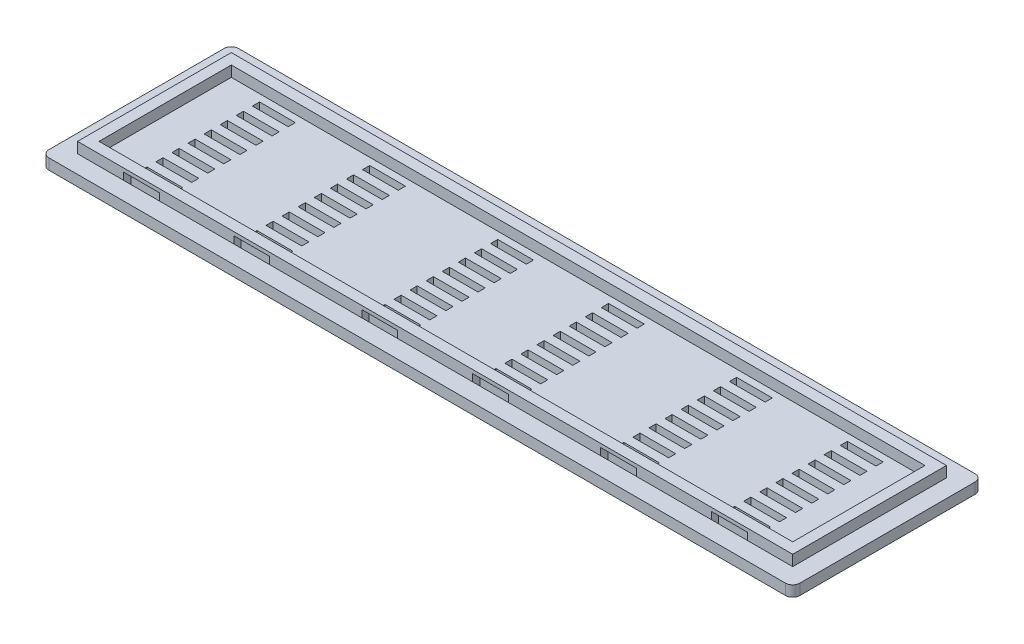
SolidWorks part; units mm, degrees
material "PET"
ref_plane "Спереди" through (0, 0, 0) normal (0, 0, 1) x (1, 0, 0)
ref_plane "Сверху" through (0, 0, 0) normal (0, 1, 0) x (1, 0, 0)
ref_plane "Справа" through (0, 0, 0) normal (1, 0, 0) x (0, 0, -1)
other "Configuration Table"
sketch "Основание & крышка" plane through (0, 0, 0) normal (0, 1, 0) x (1, 0, 0)
  line L1 (105, -26.5) -> (-105, -26.5)
  line L2 (105, -26.5) -> (105, 26.5)
  line L3 (105, 26.5) -> (-105, 26.5)
  line L4 (-105, -26.5) -> (-105, 26.5)
  line L5 (105, -26.5) -> (-105, 26.5) construction
  line L6 (105, 26.5) -> (-105, -26.5) construction
  line L7 (100, -21.5) -> (-100, -21.5)
  line L8 (100, -21.5) -> (100, 21.5)
  line L9 (100, 21.5) -> (-100, 21.5)
  line L10 (-100, -21.5) -> (-100, 21.5)
  line L11 (100, -21.5) -> (-100, 21.5) construction
  line L12 (100, 21.5) -> (-100, -21.5) construction
  point P0 (0, 0)
  point P5 (0, 0)
  dimension "D1" = 210
  dimension "D2" = 53
  dimension "D3" = 43
  dimension "D4" = 200
extrude "Бобышка-Вытянуть1" add sketch "Основание & крышка" along normal blind 50 contours L3 L4 L1 L2
sketch "Эскиз3" plane through (0, 0, 0) normal (0, -1, 0) x (1, 0, 0)
  line L0 (105, 26.5) -> (-105, 26.5) construction
  line L1 (-100, -21.5) -> (100, -21.5)
  line L2 (-100, -21.5) -> (-100, 21.5)
  line L3 (-100, 21.5) -> (100, 21.5)
  line L4 (100, -21.5) -> (100, 21.5)
  line L5 (-100, -21.5) -> (100, 21.5) construction
  line L6 (-100, 21.5) -> (100, -21.5) construction
  line L7 (105, 26.5) -> (105, -26.5) construction
  point P0 (0, 0)
  dimension "D1" = 5
  dimension "D2" = 5
extrude "Вырез-Вытянуть1" cut sketch "Эскиз3" against normal blind 45
sketch "Эскиз4" plane through (0, 50, 0) normal (0, 1, 0) x (1, 0, 0)
  line L0 (0, 41.131) -> (0, -55.5904) construction
  line L1 (105, 26.5) -> (-105, 26.5) construction
  line L2 (105, -26.5) -> (105, 26.5) construction
  line L3 (-127.2033, 0) -> (126.8125, 0) construction
  circle A0 centre (98, 19.5) radius 3.5
  circle A1 centre (-98, 19.5) radius 3.5
  circle A2 centre (98, -19.5) radius 3.5
  circle A3 centre (-98, -19.5) radius 3.5
  dimension "D1" = 7
  dimension "D3" = 7
  dimension "D2" = 7
sketch "Эскиз6" plane through (0, 50, 0) normal (0, 1, 0) x (1, 0, 0)
  line L0 (-117.6289, 0) -> (122.9046, 0) construction
  line L1 (0, 47.7745) -> (0, -57.5444) construction
extrude "Бобышка-Вытянуть2" add sketch "Эскиз4" along normal blind 2 draft 1 contours A0
fillet "Скругление2" radius 0.5 1 edges at (98, 52, -16.0349)
extrude "Бобышка-Вытянуть3" add sketch "Эскиз4<5>" along normal blind 2 contours A2
sketch "Эскиз4<5>" plane through (0, 50, 0) normal (0, 1, 0) x (1, 0, 0) same geometry as "Эскиз4"
extrude "Бобышка-Вытянуть4" add sketch "Эскиз4<6>" along normal blind 2 contours A3
sketch "Эскиз4<6>" plane through (0, 50, 0) normal (0, 1, 0) x (1, 0, 0) same geometry as "Эскиз4"
extrude "Бобышка-Вытянуть5" add sketch "Эскиз4<7>" along normal blind 2 contours A1
sketch "Эскиз4<7>" plane through (0, 50, 0) normal (0, 1, 0) x (1, 0, 0) same geometry as "Эскиз4"
fillet "Скругление3" radius 0.5 1 edges at (-98, 52, 23)
fillet "Скругление4" radius 0.5 1 edges at (-98, 52, -23)
fillet "Скругление5" radius 0.5 1 edges at (98, 52, 16)
sketch "Эскиз7" plane through (0, 0, -26.5) normal (0, 0, -1) x (-1, 0, 0)
  line L0 (0, -32.9698) -> (0, 82.1336) construction
  line L1 (-136.416, 24.5819) -> (136.5704, 24.5819) construction
  circle A0 centre (0, 35.0819) radius 6
  point P7 (0, 24.5819)
  dimension "D1" = 12
  dimension "D2" = 10.5
extrude "Вырез-Вытянуть2" cut sketch "Эскиз7" against normal blind 14 draft 5 contours A0
fillet "Скругление6" radius 2 1 edges at (-6, 35.0819, -26.5)
sketch "Эскиз8" plane through (0, 0, -21.5) normal (0, 0, 1) x (1, 0, 0)
  circle A0 centre (0, 35.0819) radius 7
  dimension "D1" = 14
extrude "Бобышка-Вытянуть6" add sketch "Эскиз8" along normal blind 7 draft 5 contours A0
sketch "Эскиз9" plane through (0, 0, -14.5) normal (0, 0, 1) x (1, 0, 0)
  circle A0 centre (0, 35.0819) radius 5.15
  dimension "D1" = 10.3
extrude "Вырез-Вытянуть3" cut sketch "Эскиз9" against normal blind 7 draft 5 draft outward yes
sketch "Эскиз10" plane through (0, 0, 26.5) normal (0, 0, 1) x (1, 0, 0)
  line L0 (0, -14.7722) -> (0, 61.6389) construction
  line L1 (-118.5615, 25) -> (116.6086, 25) construction
  line L2 (-127.2033, 50) -> (126.8125, 50) construction
  line L3 (-64.7, 38.15) -> (-35.3, 38.15)
  line L4 (-64.7, 38.15) -> (-64.7, 11.85)
  line L5 (-64.7, 11.85) -> (-35.3, 11.85)
  line L6 (-35.3, 38.15) -> (-35.3, 11.85)
  line L7 (-64.7, 38.15) -> (-35.3, 11.85) construction
  line L8 (-64.7, 11.85) -> (-35.3, 38.15) construction
  point P5 (-50, 25)
  point P13 (0, 25)
  dimension "D1" = 29.4
  dimension "D2" = 26.3
  dimension "D3" = 50
  dimension "D4" = 25
extrude "Вырез-Вытянуть4" cut sketch "Эскиз10" against normal blind 5
sketch "Эскиз13" plane through (0, 0, 21.5) normal (0, 0, -1) x (-1, 0, 0)
  line L0 (100, 45) -> (100, 0) construction
  line L1 (30.4, 38.75) -> (69.6, 38.75)
  line L2 (30.4, 38.75) -> (30.4, 11.25)
  line L3 (30.4, 11.25) -> (69.6, 11.25)
  line L4 (69.6, 38.75) -> (69.6, 11.25)
  line L5 (30.4, 38.75) -> (69.6, 11.25) construction
  line L6 (30.4, 11.25) -> (69.6, 38.75) construction
  line L8 (-100, 45) -> (100, 45) construction
  point P0 (50, 25)
  dimension "D1" = 50
  dimension "D2" = 20
  dimension "D3" = 27.5
  dimension "D4" = 39.2
extrude "Вырез-Вытянуть5" cut sketch "Эскиз13" against normal blind 2
sketch "Эскиз14" plane through (0, 0, 26.5) normal (0, 0, 1) x (1, 0, 0)
  line L0 (0, 0) -> (0, 50) construction
  line L1 (105, 0) -> (-105, 0) construction
  line L2 (105, 50) -> (-105, 50) construction
  line L3 (-105, 25) -> (105, 25) construction
  line L4 (-105, 50) -> (-105, 0) construction
  line L5 (105, 50) -> (105, 0) construction
  line L6 (-79.5, 28.8) -> (-73.5, 28.8)
  line L7 (-79.5, 15.2) -> (-73.5, 15.2)
  line L8 (-79.5, 15.2) -> (-79.5, 21.2)
  line L9 (-79.5, 21.2) -> (-73.5, 21.2)
  line L10 (-73.5, 15.2) -> (-73.5, 21.2)
  line L11 (-79.5, 15.2) -> (-73.5, 21.2) construction
  line L12 (-79.5, 21.2) -> (-73.5, 15.2) construction
  line L13 (-79.5, 28.8) -> (-73.5, 34.8) construction
  line L14 (-79.5, 34.8) -> (-79.5, 28.8)
  line L15 (-79.5, 34.8) -> (-73.5, 28.8) construction
  line L16 (-73.5, 34.8) -> (-73.5, 28.8)
  line L17 (-79.5, 34.8) -> (-73.5, 34.8)
  point P12 (-76.5, 18.2)
  point P21 (-76.5, 31.8)
  dimension "D1" = 6
  dimension "D2" = 6
  dimension "D3" = 18.2
  dimension "D4" = 25.5
extrude "Вырез-Вытянуть6" cut sketch "Эскиз14" against normal blind 5
sketch "Эскиз16" plane through (0, 0, 21.5) normal (0, 0, -1) x (-1, 0, 0)
  line L0 (-100, 45) -> (100, 45) construction
  line L1 (73.4, 34.85) -> (79.5, 34.85)
  line L2 (73.4, 34.85) -> (73.4, 28.75)
  line L3 (73.4, 28.75) -> (79.5, 28.75)
  line L4 (79.5, 34.85) -> (79.5, 28.75)
  line L5 (73.4, 34.85) -> (79.5, 28.75) construction
  line L6 (73.4, 28.75) -> (79.5, 34.85) construction
  line L7 (100, 45) -> (100, 0) construction
  point P0 (76.45, 31.8)
  dimension "D1" = 6.1
  dimension "D2" = 6.1
  dimension "D3" = 13.2
  dimension "D4" = 20.5
fillet "Скругление7" radius 2 8 edges at (-105, 25, -26.5) (-105, 50, 0) (0, 50, -26.5) (105, 25, -26.5) (105, 50, 0) (105, 25, 26.5) (-105, 25, 26.5) (0, 50, 26.5)
sketch "Эскиз17" plane through (0, 0, 0) normal (0, -1, 0) x (1, 0, 0)
  line L4 (-105, 24.5) -> (-105, -24.5)
  line L5 (-103, -26.5) -> (103, -26.5)
  line L6 (105, -24.5) -> (105, 24.5)
  line L7 (103, 26.5) -> (-103, 26.5)
  line L8 (-105, 24.5) -> (-105, -24.5)
  line L9 (-103, -26.5) -> (103, -26.5)
  line L10 (105, -24.5) -> (105, 24.5)
  line L11 (103, 26.5) -> (-103, 26.5)
  arc A4 (-105, -24.5) -> (-103, -26.5) centre (-103, -24.5) ccw
  arc A5 (103, -26.5) -> (105, -24.5) centre (103, -24.5) ccw
  arc A6 (105, 24.5) -> (103, 26.5) centre (103, 24.5) ccw
  arc A7 (-103, 26.5) -> (-105, 24.5) centre (-103, 24.5) ccw
  arc A8 (-105, -24.5) -> (-103, -26.5) centre (-103, -24.5) ccw
  arc A9 (103, -26.5) -> (105, -24.5) centre (103, -24.5) ccw
  arc A10 (105, 24.5) -> (103, 26.5) centre (103, 24.5) ccw
  arc A11 (-103, 26.5) -> (-105, 24.5) centre (-103, 24.5) ccw
  dimension "D1" = 0
extrude "Бобышка-Вытянуть8" add sketch "Эскиз17" along normal blind 3 separate body
sketch "Эскиз18" plane through (0, 0, 0) normal (0, 1, 0) x (1, 0, 0)
  line L8 (-100, -21.5) -> (100, -21.5)
  line L28 (-100, -21.5) -> (100, -21.5)
  line L32 (100, -21.5) -> (100, 21.5)
  line L34 (100, -21.5) -> (100, 21.5)
  line L36 (100, 21.5) -> (-100, 21.5)
  line L37 (100, 21.5) -> (-100, 21.5)
  line L38 (-100, 21.5) -> (-100, -21.5)
  line L39 (-100, 21.5) -> (-100, -21.5)
  dimension "D1" = 5
extrude "Крышка" add sketch "Эскиз18" along normal blind 3 from surface thin contours L37 L39 L28 L34 starting at face at (0, 0, 0) thin type one direction reverse wall 3
sketch "Эскиз20" plane through (0, -3, 0) normal (0, -1, 0) x (1, 0, 0)
  line L0 (-105, 0) -> (105, 0) construction
  line L1 (-105, 24.5) -> (-105, -24.5) construction
  line L2 (105, -24.5) -> (105, 24.5) construction
  line L3 (0, 26.5) -> (0, -26.5) construction
  line L4 (103, 26.5) -> (-103, 26.5) construction
  line L5 (-103, -26.5) -> (103, -26.5) construction
sketch "Эскиз21" plane through (0, -3, 0) normal (0, -1, 0) x (1, 0, 0)
  line L0 (-66.7, -49.4791) -> (-66.7, 41.6381) construction
  line L1 (-33.4, -45.2678) -> (-33.4, 45.8494) construction
  line L2 (33.4, -44.7574) -> (33.4, 46.3598) construction
  line L3 (66.7, -45.7783) -> (66.7, 45.3389) construction
  line L4 (105, -24.5) -> (105, 24.5) construction
  line L5 (0, 26.5) -> (0, -26.5) construction
  line L6 (0, -41.131) -> (0, 55.5904) construction
  line L7 (15.5, 60.8548) -> (15.5, -34.3859) construction
  line L8 (10.5, 21.5) -> (20.5, 21.5)
  line L9 (10.5, 21.5) -> (10.5, 19.5)
  line L10 (10.5, 19.5) -> (20.5, 19.5)
  line L11 (20.5, 21.5) -> (20.5, 19.5)
  line L12 (10.5, 21.5) -> (20.5, 19.5) construction
  line L13 (10.5, 19.5) -> (20.5, 21.5) construction
  line L26 (103, 26.5) -> (-103, 26.5) construction
  line L27 (-10.5, 19.5) -> (-20.5, 21.5) construction
  line L28 (-10.5, 21.5) -> (-20.5, 19.5) construction
  line L33 (-20.5, 21.5) -> (-20.5, 19.5)
  line L34 (-10.5, 19.5) -> (-20.5, 19.5)
  line L39 (-10.5, 21.5) -> (-10.5, 19.5)
  line L40 (-10.5, 21.5) -> (-20.5, 21.5)
  line L45 (-56.3, 21.5) -> (-46.3, 19.5) construction
  line L46 (-56.3, 19.5) -> (-46.3, 21.5) construction
  line L51 (-56.3, 21.5) -> (-46.3, 21.5)
  line L52 (-56.3, 21.5) -> (-56.3, 19.5)
  line L57 (-56.3, 19.5) -> (-46.3, 19.5)
  line L58 (-46.3, 21.5) -> (-46.3, 19.5)
  line L63 (-77.1, 19.5) -> (-87.1, 21.5) construction
  line L64 (-77.1, 21.5) -> (-87.1, 19.5) construction
  line L69 (-87.1, 21.5) -> (-87.1, 19.5)
  line L70 (-77.1, 19.5) -> (-87.1, 19.5)
  line L75 (-77.1, 21.5) -> (-77.1, 19.5)
  line L76 (-77.1, 21.5) -> (-87.1, 21.5)
  line L78 (77.3, 21.5) -> (87.3, 19.5) construction
  line L79 (77.3, 19.5) -> (87.3, 21.5) construction
  line L80 (56.3, 19.5) -> (46.3, 21.5) construction
  line L81 (56.3, 21.5) -> (46.3, 19.5) construction
  line L82 (77.3, 21.5) -> (87.3, 21.5)
  line L83 (77.3, 21.5) -> (77.3, 19.5)
  line L84 (77.3, 19.5) -> (87.3, 19.5)
  line L85 (87.3, 21.5) -> (87.3, 19.5)
  line L86 (46.3, 21.5) -> (46.3, 19.5)
  line L87 (56.3, 19.5) -> (46.3, 19.5)
  line L88 (56.3, 21.5) -> (56.3, 19.5)
  line L89 (56.3, 21.5) -> (46.3, 21.5)
  line L198 (0, 55.5904) -> (0, -41.131) construction
  point P14 (15.5, 20.5)
  point P23 (-15.5, 20.5)
  point P28 (-51.3, 20.5)
  point P31 (15.5, 21.5)
  point P38 (-82.1, 20.5)
  point P47 (82.3, 20.5)
  point P48 (51.3, 20.5)
  dimension "D1" = 38.3
  dimension "D2" = 33.3
  dimension "D3" = 33.4
  dimension "D4" = 33.4
  dimension "D5" = 33.3
  dimension "D6" = 15.5
  dimension "D7" = 10
  dimension "D8" = 2
  dimension "D9" = 5
extrude "Вырез-Вытянуть12" cut sketch "Эскиз21" against normal blind 5
pattern_linear "Линейный массив1" count 10 spacing 4.5 along (0, 0, -1) of "Вырез-Вытянуть12"
delete or keep bodies "Тело-Удалить/Сохранить 1" type keep bodies bodies 128
